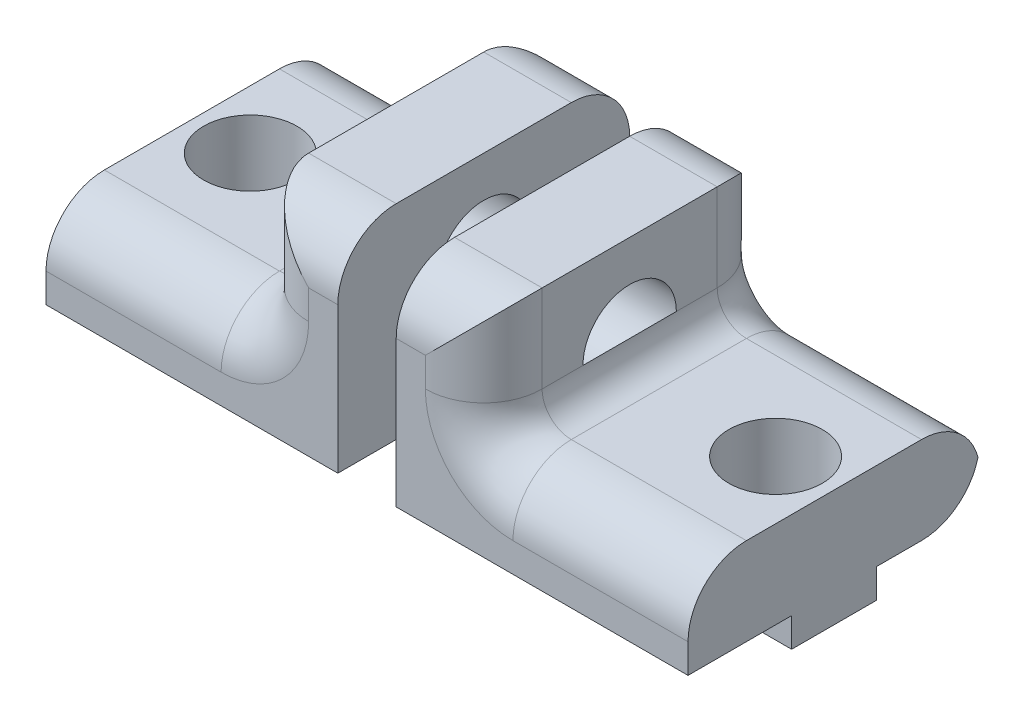
SolidWorks part; units mm, degrees
ref_plane "Front Plane" through (0, 0, 0) normal (0, 0, 1) x (1, 0, 0)
ref_plane "Top Plane" through (0, 0, 0) normal (0, 1, 0) x (1, 0, 0)
ref_plane "Right Plane" through (0, 0, 0) normal (1, 0, 0) x (0, 0, -1)
sketch "Esquisse1" plane through (0, 0, 0) normal (0, 0, 1) x (1, 0, 0)
  line L0 (0, 0) -> (10, 0)
  line L1 (10, 0) -> (10, 3)
  line L2 (10, 3) -> (4, 3)
  line L4 (3, 4) -> (3, 7)
  line L5 (3, 7) -> (0, 7)
  line L6 (0, 7) -> (0, 0)
  arc A0 (4, 3) -> (3, 4) centre (4, 4) cw
  dimension "D1" = 1
  dimension "D2" = 7
  dimension "D3" = 3
  dimension "D4" = 10
extrude "Main" add sketch "Esquisse1" along normal mid plane 10
sketch "Esquisse2" plane through (0, 0, 0) normal (-1, 0, 0) x (0, 0, 1)
  line L0 (5, 0) -> (-5, 0) construction
  line L2 (-5, 4) -> (-5, 7) construction
  circle A0 centre (0, 4) radius 1.6
  dimension "D1" = 3.2
  dimension "D2" = 4
  dimension "D3" = 5
extrude "VerticalHole" cut sketch "Esquisse2" against normal up to surface (3 mm away) and the other way through all up to face at (3, 5.5, 0)
sketch "Esquisse5" plane through (0, 0, 0) normal (0, -1, 0) x (-1, 0, 0)
  line L0 (-10, -5) -> (-10, 5) construction
  line L1 (0, 1.45) -> (-10, 1.45)
  line L2 (0, 1.45) -> (0, -1.45)
  line L3 (0, -1.45) -> (-10, -1.45)
  line L4 (-10, 1.45) -> (-10, -1.45)
  line L6 (0, -5) -> (-10, -5) construction
  line L7 (0, -5) -> (0, 5) construction
  dimension "D1" = 2.9
  dimension "D2" = 3.55
extrude "MakerBeamSupport" add sketch "Esquisse5" along normal blind 1
sketch "Esquisse3" plane through (0, 0, 0) normal (0, -1, 0) x (1, 0, 0)
  line L0 (10, 5) -> (10, 1.45) construction
  line L4 (10, -1.45) -> (10, 1.45) construction
  circle A0 centre (8, 0) radius 1.6
  point P2 (10, 0)
  dimension "D1" = 3.2
  dimension "D2" = 2
extrude "MakerBeamHole" cut sketch "Esquisse3" against normal through all both and the other way through all
fillet "Fillet1" radius 2 9 edges at (3, 5.5, -5) (3.2929, 3.2929, -5) (3, 5.5, 5) (3.2929, 3.2929, 5) (7, 3, -5) (7, 3, 5) (1.5, 7, -5) (1.5, 7, 5) (5, 0, -5)
ref_plane "Plane1" through (-1, 0, 0) normal (-1, 0, 0) x (0, 0, 1)
mirror "Mirror2" about plane through (-1, 0, 0) normal (-1, 0, 0) of bodies 110
